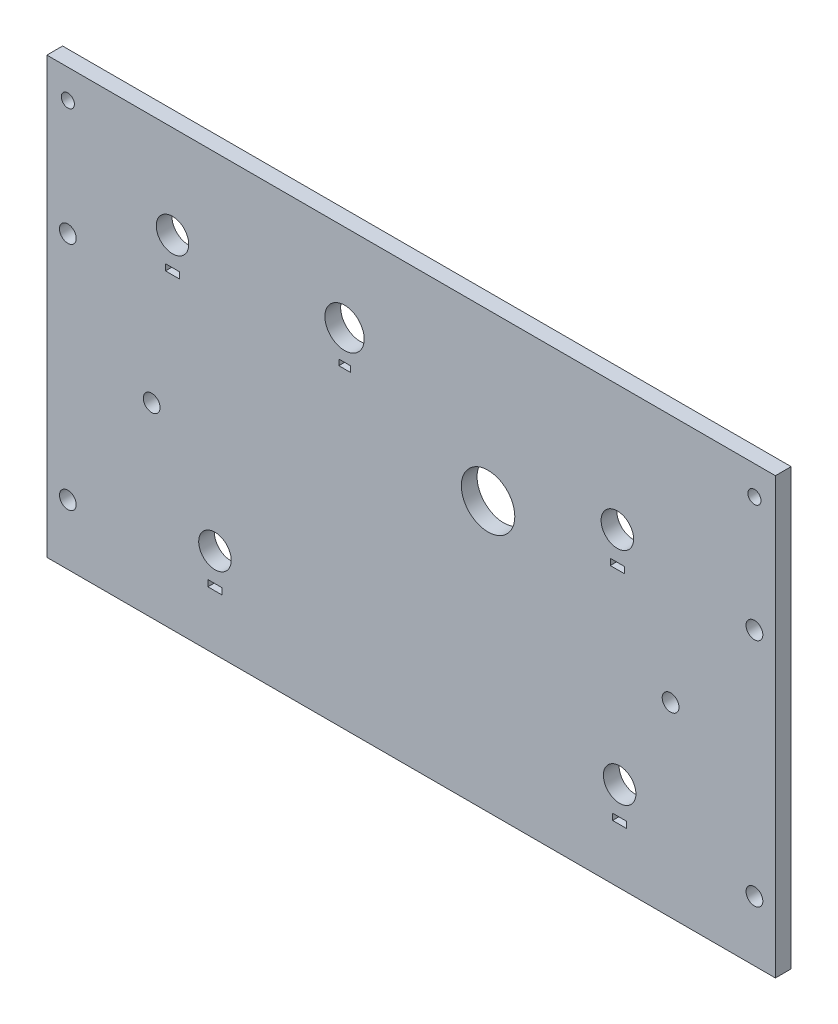
SolidWorks part; units mm, degrees
ref_plane "Front Plane" through (0, 0, 0) normal (0, 0, 1) x (1, 0, 0)
ref_plane "Top Plane" through (0, 0, 0) normal (0, 1, 0) x (1, 0, 0)
ref_plane "Right Plane" through (0, 0, 0) normal (1, 0, 0) x (0, 0, -1)
sketch "Sketch1" plane through (0, 0, 0) normal (0, 0, 1) x (1, 0, 0)
  line L0 (0, 41.5) -> (139, 41.5) construction
  line L1 (0, 0) -> (139, 0)
  line L2 (0, 0) -> (0, 83)
  line L3 (0, 83) -> (139, 83)
  line L4 (139, 0) -> (139, 83)
  line L5 (69.5, 83) -> (69.5, 0) construction
  line L8 (56.7976, 66.3275) -> (56.7976, 54.5676) construction
  line L9 (55.6976, 59.5275) -> (57.8976, 59.5275)
  line L10 (55.6976, 59.5275) -> (55.6976, 60.6275)
  line L11 (55.6976, 60.6275) -> (57.8976, 60.6275)
  line L12 (57.8976, 59.5275) -> (57.8976, 60.6275)
  line L13 (55.6976, 59.5275) -> (57.8976, 60.6275) construction
  line L14 (55.6976, 60.6275) -> (57.8976, 59.5275) construction
  line L17 (32.0701, 17.1004) -> (32.0701, 11.1004) construction
  line L30 (30.7201, 10.5004) -> (33.4201, 10.5004)
  line L31 (30.7201, 10.5004) -> (30.7201, 11.7004)
  line L43 (30.7201, 11.7004) -> (33.4201, 11.7004)
  line L44 (33.4201, 10.5004) -> (33.4201, 11.7004)
  line L45 (30.7201, 10.5004) -> (33.4201, 11.7004) construction
  line L50 (30.7201, 11.7004) -> (33.4201, 10.5004) construction
  line L51 (109.2813, 17.1004) -> (109.2813, 11.1004) construction
  line L52 (108.8427, 59) -> (108.8427, 53) construction
  line L57 (107.4927, 52.4) -> (110.1927, 52.4)
  line L58 (107.4927, 52.4) -> (107.4927, 53.6)
  line L59 (107.4927, 53.6) -> (110.1927, 53.6)
  line L64 (110.1927, 52.4) -> (110.1927, 53.6)
  line L65 (107.4927, 52.4) -> (110.1927, 53.6) construction
  line L66 (23.9669, 65.2477) -> (23.9669, 59.2477) construction
  line L67 (22.6169, 58.6477) -> (25.3169, 58.6477)
  line L68 (22.6169, 58.6477) -> (22.6169, 59.8477)
  line L69 (22.6169, 59.8477) -> (25.3169, 59.8477)
  line L70 (25.3169, 58.6477) -> (25.3169, 59.8477)
  line L71 (22.6169, 58.6477) -> (25.3169, 59.8477) construction
  line L72 (22.6169, 59.8477) -> (25.3169, 58.6477) construction
  line L80 (107.4927, 53.6) -> (110.1927, 52.4) construction
  line L82 (107.9313, 10.5004) -> (110.6313, 10.5004)
  line L83 (107.9313, 10.5004) -> (107.9313, 11.7004)
  line L84 (107.9313, 11.7004) -> (110.6313, 11.7004)
  line L85 (110.6313, 10.5004) -> (110.6313, 11.7004)
  line L86 (107.9313, 10.5004) -> (110.6313, 11.7004) construction
  line L87 (107.9313, 11.7004) -> (110.6313, 10.5004) construction
  circle A4 centre (4, 55.5) radius 1.6
  circle A5 centre (135, 55.5) radius 1.6
  circle A6 centre (135, 11.5) radius 1.6
  circle A7 centre (4, 11.5) radius 1.6
  circle A9 centre (20, 35.5283) radius 1.6
  circle A10 centre (56.7976, 66.3275) radius 3.75
  circle A11 centre (119, 35.5283) radius 1.6
  circle A19 centre (23.9669, 65.2477) radius 3.1
  circle A21 centre (32.0701, 17.1004) radius 3.1
  circle A22 centre (109.2813, 17.1004) radius 3.1
  circle A23 centre (84.179, 51.3806) radius 5.1
  circle A24 centre (108.8427, 59) radius 3.1
  circle A27 centre (135, 77.5) radius 1.25
  circle A28 centre (4, 77.5) radius 1.25
  point P15 (56.7976, 60.0775)
  point P32 (108.8427, 53)
  point P39 (32.0701, 11.1004)
  point P47 (109.2813, 11.1004)
  point P65 (48.6584, 50.7867)
  point P116 (23.9669, 59.2477)
  dimension "D8" = 3.2
  dimension "D19" = 3.2
  dimension "D6" = 7.5
  dimension "D16" = 6.2
  dimension "D17" = 10.2
  dimension "D27" = 2.5
  dimension "D1" = 139
  dimension "D2" = 83
  dimension "D13" = 27.5
  dimension "D11" = 131
  dimension "D12" = 4
  dimension "D20" = 4
  dimension "D18" = 20
  dimension "D3" = 11.5
  dimension "D4" = 2.2
  dimension "D5" = 1.1
  dimension "D7" = 5.7
  dimension "D50" = 1.2
  dimension "D51" = 6
  dimension "D15" = 20
  dimension "D24" = 6
  dimension "D26" = 6
  dimension "D22" = 6
  dimension "D14" = 44
  dimension "D28" = 5.5
  dimension "D29" = 4
  dimension "D30" = 4
  dimension "D31" = 24
  dimension "D32" = 2.7
  dimension "D9" = 2
  dimension "D10" = 2
extrude "Boss-Extrude1" add sketch "Sketch1" along normal blind 3
equation "\"D13@Sketch1\"=22+5.5"
